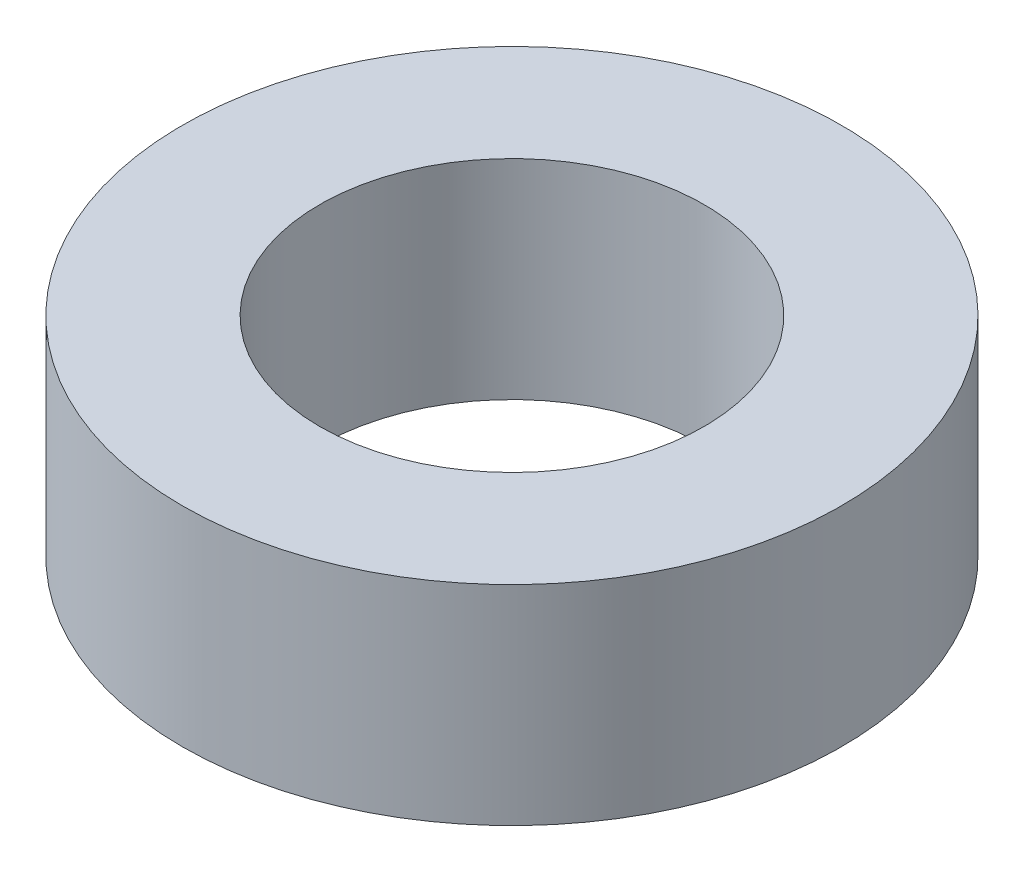
SolidWorks part; units mm, degrees
ref_plane "Front Plane" through (0, 0, 0) normal (0, 0, 1) x (1, 0, 0)
ref_plane "Top Plane" through (0, 0, 0) normal (0, 1, 0) x (1, 0, 0)
ref_plane "Right Plane" through (0, 0, 0) normal (1, 0, 0) x (0, 0, -1)
sketch "Sketch1" plane through (0, 0, 0) normal (0, 1, 0) x (1, 0, 0)
  circle A0 centre (0, 0) radius 30
  dimension "FLANGE_OD" = 60
extrude "Boss-Extrude1" add sketch "Sketch1" along normal blind 19
sketch "Sketch2" plane through (0, 0, 0) normal (0, 1, 0) x (1, 0, 0)
  circle A0 centre (0, 0) radius 17.5
  dimension "BORE_D" = 35
extrude "Cut-Extrude1" cut sketch "Sketch2" along normal through all
sketch "Sketch3" plane through (0, 19, 0) normal (0, 1, 0) x (1, 0, 0)
  circle A0 centre (0, 0) radius 12.0029 construction
  circle A1 centre (-12.0029, 0) radius 1.5465
  dimension "BOLT_D" = 3.093
  dimension "BOLT_PCD" = 24.0058
extrude "Cut-Extrude2" cut sketch "Sketch3" against normal blind 15.4834 rebuild error yes
pattern_circular "CirPattern1" count 5 over 360 rebuild error yes
